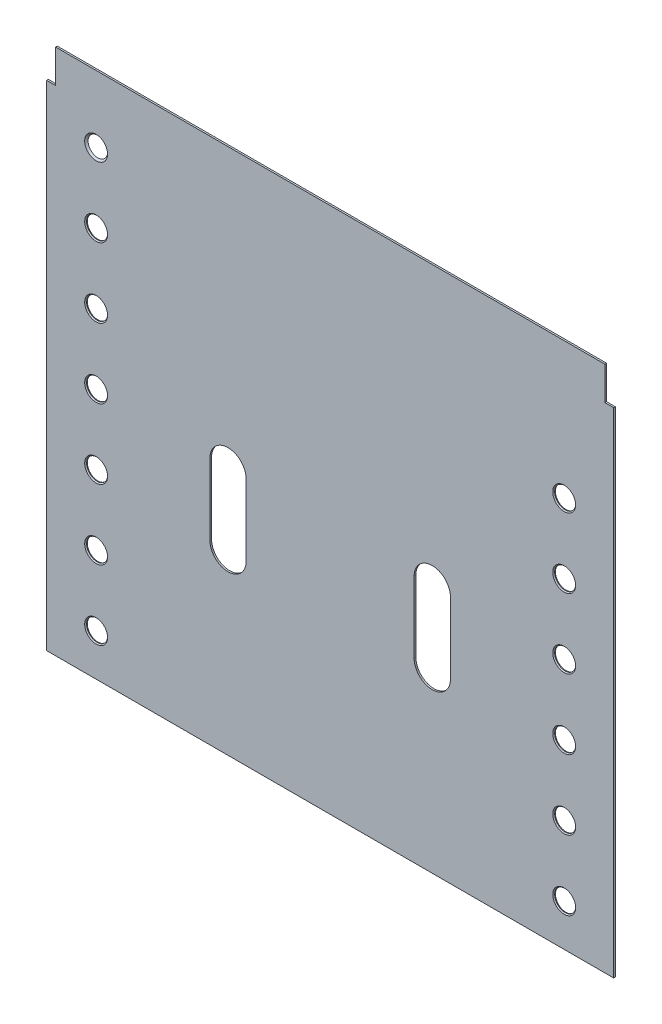
SolidWorks part; units mm, degrees
ref_plane "Front Plane" through (0, 0, 0) normal (0, 0, 1) x (1, 0, 0)
ref_plane "Top Plane" through (0, 0, 0) normal (0, 1, 0) x (1, 0, 0)
ref_plane "Right Plane" through (0, 0, 0) normal (1, 0, 0) x (0, 0, -1)
sketch "Sketch1" plane through (0, 0, 0) normal (0, 0, -1) x (1, 0, 0)
  line L1 (-203.2, 237) -> (0, 237)
  line L2 (-203.2, 237) -> (-203.2, 60)
  line L3 (-203.2, 60) -> (0, 60)
  line L4 (0, 237) -> (0, 60)
  dimension "D2" = 203.2
  dimension "D3" = 177
extrude "Boss-Extrude1" add sketch "Sketch1" along normal blind 0.6096
sketch "Sketch2" plane through (0, 0, -0.6096) normal (0, 0, -1) x (1, 0, 0)
  line L0 (-138.2, 180) -> (-138.2, 141.5) construction
  line L1 (0, 237) -> (-203.2, 237) construction
  line L2 (-138.2, 180) -> (-138.2, 237) construction
  line L3 (-138.2, 173.5) -> (-138.2, 148) construction
  line L6 (-131.7, 173.5) -> (-131.7, 148)
  line L7 (-144.7, 173.5) -> (-144.7, 148)
  line L8 (-138.2, 160.75) -> (-203.2, 160.75) construction
  line L9 (-203.2, 237) -> (-203.2, 60) construction
  line L10 (-65, 180) -> (-65, 141.5) construction
  line L11 (-65, 180) -> (-65, 237) construction
  line L12 (-65, 173.5) -> (-65, 148) construction
  line L16 (-58.5, 173.5) -> (-58.5, 148)
  line L17 (-71.5, 173.5) -> (-71.5, 148)
  line L18 (-65, 160.75) -> (0, 160.75) construction
  line L19 (0, 60) -> (0, 237) construction
  arc A2 (-131.7, 173.5) -> (-144.7, 173.5) centre (-138.2, 173.5) ccw
  arc A3 (-144.7, 148) -> (-131.7, 148) centre (-138.2, 148) ccw
  arc A6 (-58.5, 173.5) -> (-71.5, 173.5) centre (-65, 173.5) ccw
  arc A7 (-71.5, 148) -> (-58.5, 148) centre (-65, 148) ccw
  point P5 (-138.2, 160.75)
  point P18 (-65, 160.75)
  dimension "D4" = 6.5
  dimension "D6" = 57
  dimension "D5" = 6.5
  dimension "D1" = 65
  dimension "D2" = 57
  dimension "D3" = 38.5
  dimension "D7" = 65
  dimension "D8" = 38.5
extrude "Cut-Extrude7" cut sketch "Sketch2" against normal through all
ref_plane "Plane1" through (-101.6, 0, 0) normal (1, 0, 0) x (0, 0, -1)
sketch "Sketch4" plane through (0, 0, 0) normal (0, 0, 1) x (1, 0, 0)
  line L0 (-203.2, -60) -> (0, -60) construction
  line L1 (-3.175, -60) -> (-200.025, -60)
  line L2 (-3.175, -60) -> (-3.175, -60.6096)
  line L3 (-3.175, -60.6096) -> (-200.025, -60.6096)
  line L4 (-200.025, -60) -> (-200.025, -60.6096)
  line L5 (-3.175, -237) -> (-3.175, 2) construction
  line L6 (-200.025, 2) -> (-200.025, -237) construction
  dimension "D1" = 0.6096
extrude "Boss-Extrude2" add sketch "Sketch4" along normal blind 12
sketch "Sketch8" plane through (0, 0, -0.6096) normal (0, 0, -1) x (-1, 0, 0)
  circle A0 centre (185.47, -222) radius 3.75
  circle A1 centre (185.47, -197) radius 3.75
  circle A2 centre (185.47, -172) radius 3.75
  circle A3 centre (185.47, -147) radius 3.75
  circle A4 centre (185.47, -122) radius 3.75
  circle A5 centre (185.47, -97) radius 3.75
  dimension "D1" = 7.5
extrude "Cut-Extrude8" cut sketch "Sketch8" against normal up to surface (0.6096 mm away) up to face at (-65, -160.75, 0)
mirror "Mirror1" about plane through (-101.6, 0, 0) normal (1, 0, 0) of "Cut-Extrude8"
hole_wizard "CSK for M3.5 Flat Head Machine Screw1" positions "Sketch11" profile "Sketch12" countersink size "M3.5" standard "ANSI Metric" end condition through all
sketch "Sketch11" plane through (0, 0, 0) normal (0, 0, 1) x (1, 0, 0)
  point P0 (-185.47, -72)
  point P3 (-185.47, -97)
  point P6 (-185.47, -122)
  point P9 (-185.47, -147)
  point P12 (-185.47, -172)
  point P15 (-185.47, -197)
  point P21 (-17.73, -222)
  point P24 (-17.73, -197)
  point P27 (-17.73, -172)
  point P30 (-17.73, -147)
  point P32 (-17.73, -122)
  point P35 (-17.73, -97)
  point P38 (-185.47, -222)
  point P42 (0, 0)
sketch "Sketch12" plane through (-185.47, -72, 0) normal (1, 0, 0) x (0, -1, 0)
  line L0 (0, 0) -> (0, 0.6096)
  line L1 (0, 0.6096) -> (1.85, 0.6096)
  line L2 (1.85, 0.6096) -> (1.85, 2.25)
  line L3 (1.85, 2.25) -> (4.1, 0)
  line L5 (4.1, 0) -> (0, 0)
  line L6 (-1.85, 2.25) -> (-4.1, 0) construction
  line L11 (0, -6.35) -> (0, 107.95) construction
  dimension "Thru Hole Dia." = 3.7
  dimension "Thru Hole Depth" = 0.6096
  dimension "Near C'Sink Dia." = 8.2
  dimension "Near C'Sink Angle" = 90
sketch "Sketch13" plane through (0, 0, 12) normal (0, 0, 1) x (1, 0, 0)
  line L1 (-3.175, -60.6096) -> (-200.025, -60.6096)
  line L2 (-3.175, -60.6096) -> (-3.175, -60)
  line L3 (-3.175, -60) -> (-200.025, -60)
  line L4 (-200.025, -60.6096) -> (-200.025, -60)
sketch "Sketch14" plane through (0, 0, 0) normal (0, 0, 1) x (1, 0, 0)
  line L1 (-3.175, -60) -> (-200.025, -60)
  line L2 (-3.175, -60) -> (-3.175, -48.062)
  line L3 (-3.175, -48.062) -> (-200.025, -48.062)
  line L4 (-200.025, -60) -> (-200.025, -48.062)
  dimension "D1" = 11.938
extrude "Boss-Extrude3" add sketch "Sketch14" against normal up to surface (0.6096 mm away) up to face at (-188.9604, -72, -0.6096)
extrude "Cut-Extrude9" cut sketch "Sketch13" against normal up to surface (12 mm away) up to face at (-181.37, -72, 0)
